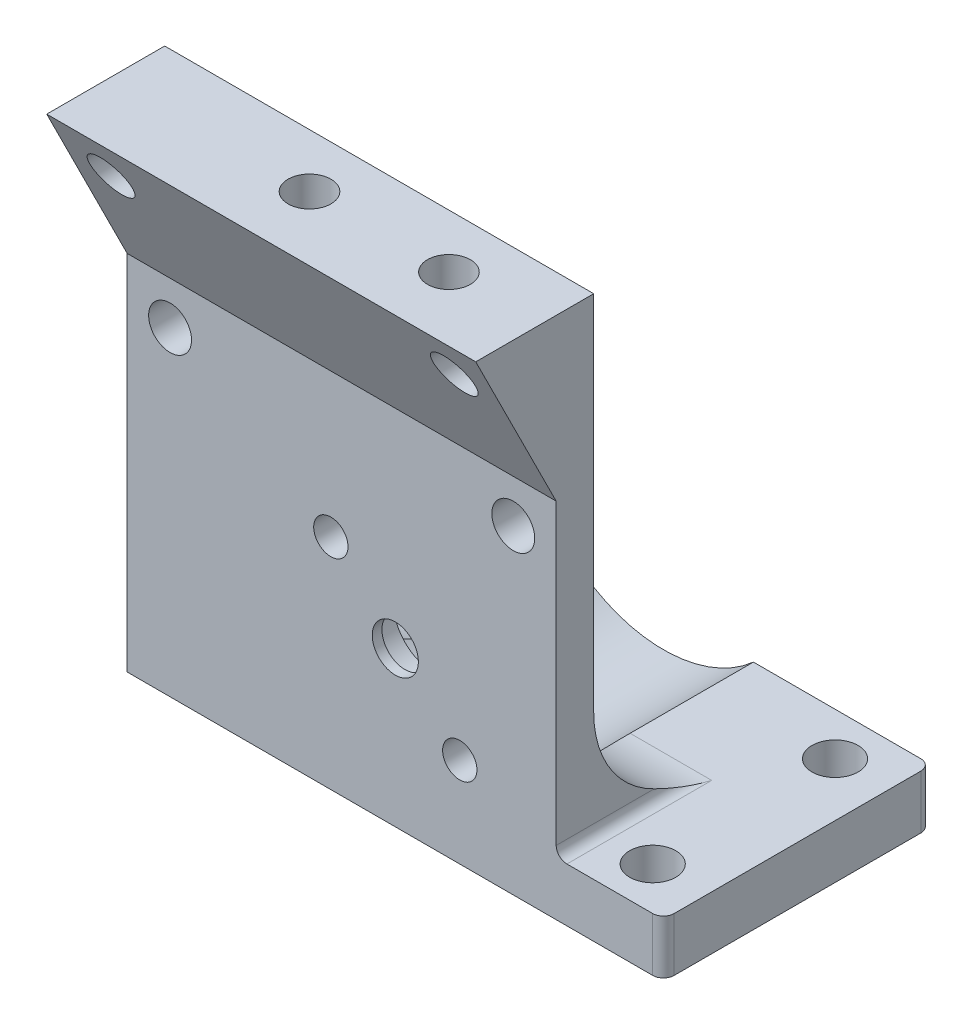
SolidWorks part; units mm, degrees
material "ABS"
ref_plane "Front Plane" through (0, 0, 0) normal (0, 0, 1) x (1, 0, 0)
ref_plane "Top Plane" through (0, 0, 0) normal (0, 1, 0) x (1, 0, 0)
ref_plane "Right Plane" through (0, 0, 0) normal (1, 0, 0) x (0, 0, -1)
other "Bounding Box"
ref_plane "Default Plane" through (-25, -14.4, -21.5) normal (0, 1, 0) x (1, 0, 0)
sketch "Sketch1" plane through (0, 0, 0) normal (0, 0, 1) x (1, 0, 0)
  line L0 (-6.0104, 6.0104) -> (6.0104, -6.0104) construction
  line L1 (-23.3521, 0) -> (49976.6479, 0) construction
  circle A0 centre (0, 0) radius 15
  circle A1 centre (-6.0104, 6.0104) radius 1.6
  circle A2 centre (6.0104, -6.0104) radius 1.6
  circle A3 centre (0, 0) radius 2.15
  dimension "D3" = 3.2
  dimension "D4" = 30
  dimension "D5" = 4.3
  dimension "D1" = 17
  dimension "D2" = 45
extrude "Boss-Extrude1" add sketch "Sketch1" along normal blind 3.5
sketch "Sketch2" plane through (0, 0, 3.5) normal (0, 0, 1) x (1, 0, 0)
  line L0 (0, 0) -> (-25, -9.4) construction
  line L1 (-25, -9.4) -> (25, -9.4)
  line L2 (-25, -9.4) -> (-25, -14.4)
  line L3 (-25, -14.4) -> (25, -14.4)
  line L4 (25, -9.4) -> (25, -14.4)
  line L5 (0, 0) -> (25, -9.4) construction
  line L7 (-25, 14.4) -> (25, 14.4) construction
  line L8 (-25, 14.4) -> (-25, 9.4) construction
  line L9 (-25, 9.4) -> (25, 9.4) construction
  line L10 (25, 14.4) -> (25, 9.4) construction
  circle A0 centre (0, 0) radius 2.15 construction
  dimension "D1" = 5
  dimension "D2" = 9.4
  dimension "D3" = 50
  dimension "D4" = 9.4
extrude "Boss-Extrude2" add sketch "Sketch2" against normal blind 25
sketch "Sketch3" plane through (0, -9.4, 0) normal (0, 1, 0) x (1, 0, 0)
  line L0 (-25, 21.5) -> (-20, 17.5) construction
  line L1 (-20, 17.5) -> (20, 17.5) construction
  line L2 (-20, 17.5) -> (-20, 0.5) construction
  line L3 (-20, 0.5) -> (20, 0.5) construction
  line L4 (20, 17.5) -> (20, 0.5) construction
  line L5 (-20, 0.5) -> (-25, -3.5) construction
  line L6 (20, 0.5) -> (25, -3.5) construction
  circle A0 centre (-20, 17.5) radius 2.15
  circle A1 centre (20, 17.5) radius 2.15
  circle A2 centre (20, 0.5) radius 2.15
  circle A3 centre (-20, 0.5) radius 2.15 construction
  dimension "D3" = 4.3
  dimension "D1" = 40
  dimension "D2" = 17
extrude "Cut-Extrude1" cut sketch "Sketch3" against normal through all and the other way through all
sketch "Sketch4" plane through (0, 0, 3.5) normal (0, 0, 1) x (1, 0, 0)
  line L0 (-4.2, 14.4) -> (4.2, 14.4)
  line L1 (-4.2, -14.4) -> (4.2, -14.4)
  line L2 (-4.2, -14.4) -> (-4.2, -15)
  line L3 (-4.2, -15) -> (4.2, -15)
  line L4 (4.2, -14.4) -> (4.2, -15)
  arc A0 (-4.2, -14.4) -> (4.2, -14.4) centre (0, 0) ccw construction
  arc A1 (-4.2, 14.4) -> (4.2, 14.4) centre (0, 0) cw
  arc A2 (11.6893, -9.4) -> (-11.6893, -9.4) centre (0, 0) ccw construction
  point P12 (0, 0)
  point P18 (0, 0)
extrude "Cut-Extrude2" cut sketch "Sketch4" against normal through all
sketch "Sketch5" plane through (0, 0, 3.5) normal (0, 0, 1) x (1, 0, 0)
  line L10 (-4.2, 14.4) -> (-25, 14.4)
  line L11 (-25, 14.4) -> (-25, -9.4)
  line L12 (-11.6893, -9.4) -> (-25, -9.4) construction
  line L13 (-25, -9.4) -> (-11.6893, -9.4)
  line L14 (4.2, 14.4) -> (25, 14.4)
  line L15 (25, 14.4) -> (25, -9.4)
  line L16 (25, -9.4) -> (11.6893, -9.4) construction
  line L17 (25, -9.4) -> (11.6893, -9.4)
  line L18 (25, -14.4) -> (25, -9.4) construction
  arc A0 (-4.2, 14.4) -> (-11.6893, -9.4) centre (0, 0) ccw construction
  arc A1 (11.6893, -9.4) -> (4.2, 14.4) centre (0, 0) ccw construction
  arc A2 (11.6893, -9.4) -> (4.2, 14.4) centre (0, 0) ccw
  arc A3 (-4.2, 14.4) -> (-11.6893, -9.4) centre (0, 0) ccw
  point P8 (25, -9.4)
  point P11 (-25, -9.4)
extrude "Boss-Extrude3" add sketch "Sketch5" against normal up to surface (3.5 mm away) up to face at (2.15, 0, 0)
sketch "Sketch6" plane through (0, 0, 0) normal (0, 0, -1) x (-1, 0, 0)
  circle A0 centre (0, 0) radius 3.65
  dimension "D1" = 7.3
extrude "Cut-Extrude3" cut sketch "Sketch6" against normal blind 2.6
sketch "Sketch7" plane through (0, 0, -21.5) normal (0, 0, -1) x (-1, 0, 0)
  circle A0 centre (0, 0) radius 12.6
  dimension "D1" = 25.2
extrude "Cut-Extrude4" cut sketch "Sketch7" against normal up to surface (21.5 mm away) up to face at (-3.65, 0, 0)
sketch "Sketch8" plane through (0, 0, 3.5) normal (0, 0, 1) x (1, 0, 0)
  line L0 (-25, 14.4) -> (25, 14.4) construction
  line L1 (-25, 14.4) -> (15, 14.4)
  line L2 (-25, 14.4) -> (-25, 34.4)
  line L3 (-25, 34.4) -> (15, 34.4)
  line L4 (15, 14.4) -> (15, 34.4)
  line L5 (-25, 14.4) -> (15, 34.4) construction
  line L6 (-25, 34.4) -> (15, 14.4) construction
  line L7 (-25, 14.4) -> (25, 14.4) construction
  point P4 (-5, 24.4)
  point P7 (23.7199, 14.4)
  point P8 (10.8948, 14.4)
  point P11 (0, 0)
  dimension "D1" = 40
  dimension "D2" = 20
extrude "Boss-Extrude4" add sketch "Sketch8" against normal up to surface (3.5 mm away) up to face at (5, -3.85, 0)
sketch "Sketch12" plane through (-25, 0, 0) normal (-1, 0, 0) x (0, 0, 1)
  line L0 (3.5, 34.4) -> (11, 34.4)
  line L1 (11, 34.4) -> (3.5, 19.4)
  line L2 (3.5, 19.4) -> (3.5, 34.4)
  line L3 (3.5, 34.4) -> (3.5, -14.4) construction
  point P5 (4.5, 14.0781)
  dimension "D1" = 7.5
  dimension "D2" = 15
extrude "Boss-Extrude7" add sketch "Sketch12" against normal up to surface (40 mm away) up to face at (15, 24.4, 1.75)
sketch "Sketch13" plane through (0, 34.4, 0) normal (0, 1, 0) x (1, 0, 0)
  line L0 (-6.5, -5) -> (0, 0) construction
  line L1 (0, 0) -> (6.5, -5) construction
  line L2 (-25, 0) -> (15, 0) construction
  circle A0 centre (-6.5, -5) radius 2
  circle A1 centre (6.5, -5) radius 2
  dimension "D1" = 4
  dimension "D2" = 13
  dimension "D3" = 5
extrude "Cut-Extrude8" cut sketch "Sketch13" against normal blind 6
sketch "Sketch14" plane through (0, 0, 0) normal (0, 0, -1) x (-1, 0, 0)
  line L0 (-15, 34.4) -> (-15, 14.4) construction
  line L1 (25, 34.4) -> (-15, 34.4) construction
  line L2 (25, -9.4) -> (25, 34.4) construction
  circle A0 centre (-11, 30.4) radius 2
  circle A1 centre (-11, 15.4) radius 2
  circle A2 centre (21, 30.4) radius 2
  circle A3 centre (21, 15.4) radius 2
  point P12 (0, 0)
  point P13 (0, 0)
  point P14 (0, 0)
  point P15 (0, 0)
  dimension "D1" = 4
  dimension "D2" = 15
  dimension "D3" = 4
  dimension "D5" = 4
  dimension "D4" = 4
extrude "Cut-Extrude9" cut sketch "Sketch14" against normal up to next
sketch "Sketch15" plane through (0, 0, 0) normal (0, 0, -1) x (-1, 0, 0)
  line L0 (-15, 14.4) -> (-25, 14.4) construction
  line L1 (-25, 14.4) -> (-15, 14.4)
  line L2 (-25, 14.4) -> (-25, -9.4)
  line L3 (-25, -9.4) -> (-15, -9.4)
  line L4 (-15, 14.4) -> (-15, -9.4)
  line L5 (-25, 14.4) -> (-15, -9.4) construction
  line L6 (-25, -9.4) -> (-15, 14.4) construction
  line L8 (-15, 34.4) -> (-15, 14.4) construction
  line L9 (-25, -9.4) -> (-8.3905, -9.4) construction
  point P4 (-20, 2.5)
  point P7 (-15, -9.4)
  point P9 (0, 0)
  point P12 (-27.3823, 14.4)
extrude "Cut-Extrude10" cut sketch "Sketch15" against normal through all
fillet "Fillet4" radius 1 3 edges at (25, -11.9, -21.5) (15, -9.4, 1.75) (25, -11.9, 3.5)
fillet "Fillet5" radius 10 2 edges at (12.1952, -9.4, 0) (-16.6952, -9.4, 0)
